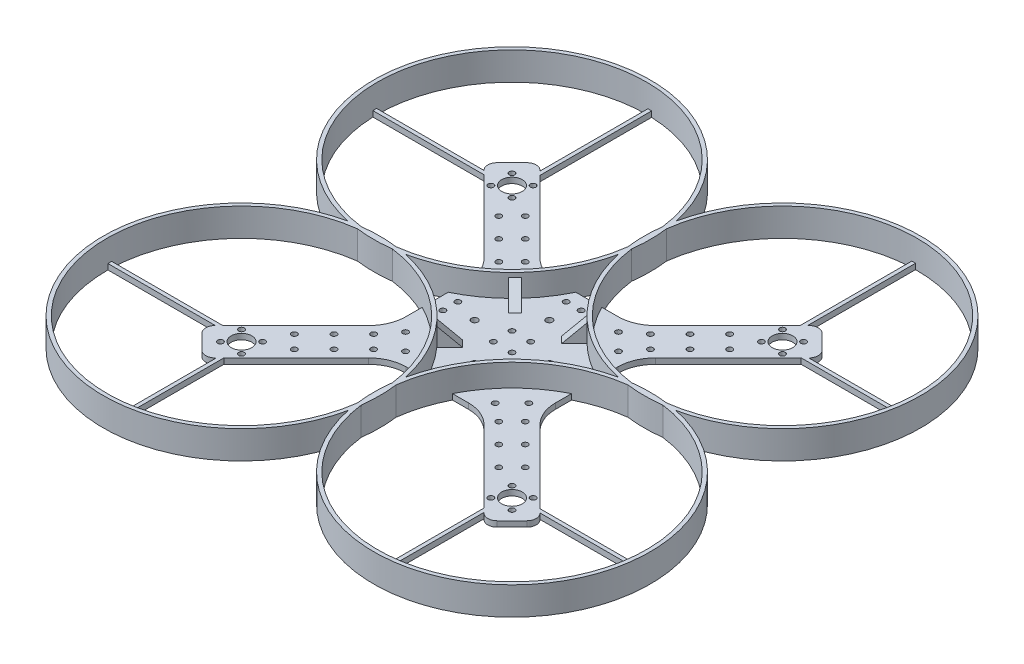
SolidWorks part; units mm, degrees
ref_plane "Front Plane" through (0, 0, 0) normal (0, 0, 1) x (1, 0, 0)
ref_plane "Top Plane" through (0, 0, 0) normal (0, 1, 0) x (1, 0, 0)
ref_plane "Right Plane" through (0, 0, 0) normal (1, 0, 0) x (0, 0, -1)
sketch "Sketch1" plane through (0, 0, 0) normal (0, 1, 0) x (1, 0, 0)
  line L0 (30.8579, 45.8579) -> (71.9645, 86.9645)
  line L1 (0, 0) -> (40, 0)
  line L2 (0, 0) -> (0, 40)
  line L3 (0, 40) -> (16.7157, 40)
  line L4 (40, 0) -> (40, 16.7157)
  line L5 (79.0355, 86.9645) -> (86.9645, 79.0355)
  line L6 (86.9645, 71.9645) -> (45.8579, 30.8579)
  arc A0 (45.8579, 30.8579) -> (40, 16.7157) centre (60, 16.7157) ccw
  arc A1 (30.8579, 45.8579) -> (16.7157, 40) centre (16.7157, 60) cw
  arc A2 (86.9645, 79.0355) -> (86.9645, 71.9645) centre (83.4289, 75.5) cw
  arc A3 (71.9645, 86.9645) -> (79.0355, 86.9645) centre (75.5, 83.4289) cw
  point P1 (83, 83)
  point P11 (40, 25)
  point P14 (25, 40)
  dimension "D7" = 20
  dimension "D8" = 5
  dimension "D1" = 40
  dimension "D2" = 40
  dimension "D3" = 45
  dimension "D4" = 25
  dimension "D5" = 25
  dimension "D6" = 83
extrude "Boss-Extrude1" add sketch "Sketch1" along normal blind 3
sketch "Sketch2" plane through (0, 3, 0) normal (0, 1, 0) x (1, 0, 0)
  line L0 (83, 83) -> (72.3934, 72.3934) construction
  line L1 (86.9645, 79.0355) -> (79.0355, 86.9645) construction
  line L2 (45.8579, 30.8579) -> (86.9645, 71.9645) construction
  circle A0 centre (72.3934, 72.3934) radius 5.5
  dimension "D1" = 11
  dimension "D2" = 15
extrude "Cut-Extrude1" cut sketch "Sketch2" against normal through all
sketch "Sketch3" plane through (0, 3, 0) normal (0, 1, 0) x (1, 0, 0)
  line L0 (72.3934, 72.3934) -> (66.7365, 66.7365) construction
  line L1 (45.8579, 30.8579) -> (86.9645, 71.9645) construction
  line L2 (72.3934, 72.3934) -> (78.0503, 66.7365) construction
  line L3 (72.3934, 72.3934) -> (66.7365, 78.0503) construction
  line L4 (72.3934, 72.3934) -> (78.0503, 78.0503) construction
  circle A0 centre (66.7365, 78.0503) radius 1.5
  circle A1 centre (66.7365, 66.7365) radius 1.5
  circle A2 centre (78.0503, 66.7365) radius 1.5
  circle A3 centre (78.0503, 78.0503) radius 1.5
  dimension "D4" = 3
  dimension "D5" = 3
  dimension "D6" = 3
  dimension "D8" = 3
  dimension "D1" = 8
  dimension "D2" = 8
  dimension "D3" = 8
  dimension "D7" = 8
extrude "Cut-Extrude2" cut sketch "Sketch3" against normal through all
sketch "Sketch4" plane through (0, 0, 0) normal (0, 1, 0) x (1, 0, 0)
  circle A0 centre (72.3934, 72.3934) radius 74
  circle A1 centre (72.3934, 72.3934) radius 72
extrude "Boss-Extrude2" add sketch "Sketch4" along normal blind 15
sketch "Sketch6" plane through (0, 3, 0) normal (0, 1, 0) x (1, 0, 0)
  line L0 (33, 4) -> (33, 24) construction
  line L1 (33, 24) -> (24, 33) construction
  line L2 (24, 33) -> (4, 33) construction
  line L3 (0, 40) -> (0, 0) construction
  line L4 (5.8602, 40) -> (0, 40) construction
  line L5 (0, 0) -> (40, 0) construction
  line L6 (40, 0) -> (40, 5.8602) construction
  line L7 (15.6066, 15.6066) -> (5, 5) construction
  line L8 (45.8579, 30.8579) -> (86.9645, 71.9645) construction
  circle A0 centre (33, 24) radius 1.5
  circle A1 centre (24, 33) radius 1.5
  circle A2 centre (4, 33) radius 1.5
  circle A3 centre (33, 4) radius 1.5
  circle A4 centre (5, 5) radius 1.5
  circle A5 centre (0, 20) radius 1.75
  circle A6 centre (20, 0) radius 1.75
  point P28 (0.2385, 3.3238)
  dimension "D1" = 4
  dimension "D7" = 5
  dimension "D11" = 3.5
  dimension "D12" = 3.5
  dimension "D2" = 7
  dimension "D3" = 20
  dimension "D4" = 4
  dimension "D5" = 20
  dimension "D6" = 7
  dimension "D8" = 5
  dimension "D9" = 15
extrude "Cut-Extrude3" cut sketch "Sketch6" against normal through all
sketch "Sketch7" plane through (0, 3, 0) normal (0, 1, 0) x (1, 0, 0)
  line L0 (54.7157, 61.7868) -> (61.7868, 54.7157) construction
  line L1 (58.2513, 58.2513) -> (83, 83) construction
  line L2 (86.9645, 79.0355) -> (79.0355, 86.9645) construction
  line L3 (45.8579, 30.8579) -> (86.9645, 71.9645) construction
  circle A0 centre (54.7157, 61.7868) radius 1.5
  circle A1 centre (61.7868, 54.7157) radius 1.5
  dimension "D1" = 10
  dimension "D2" = 35
extrude "Cut-Extrude4" cut sketch "Sketch7" against normal through all
pattern_linear "LPattern1" count 3 spacing 15 along (-0.7071, 0, 0.7071) of "Cut-Extrude4"
sketch "Sketch8" plane through (0, 3, 0) normal (0, 1, 0) x (1, 0, 0)
  line L0 (18.2404, 23.4201) -> (21.7206, 19.9399)
  line L1 (18.2404, 23.4201) -> (10.6867, 15.8663)
  line L2 (21.7206, 19.9399) -> (14.1669, 12.3861)
  line L3 (10.6867, 15.8663) -> (14.1669, 12.3861)
  line L4 (45.8579, 30.8579) -> (86.9645, 71.9645) construction
extrude "Boss-Extrude3" add sketch "Sketch8" along normal blind 10
sketch "Sketch9" plane through (0, 0, 0) normal (0, 1, 0) x (1, 0, 0)
  line L0 (70.6198, 146.3721) -> (70.6198, 145.0533) construction
  line L1 (71.6198, 82.3336) -> (69.6198, 82.3336)
  line L2 (71.6198, 82.3336) -> (71.6198, 145.0533)
  line L3 (71.6198, 145.0533) -> (69.6198, 145.0533)
  line L4 (69.6198, 82.3336) -> (69.6198, 145.0533)
  line L5 (146.3784, 70.9016) -> (145.0445, 70.9016) construction
  line L6 (82.4423, 71.9016) -> (145.0445, 71.9016)
  line L7 (82.4423, 71.9016) -> (82.4423, 69.9016)
  line L8 (82.4423, 69.9016) -> (145.0445, 69.9016)
  line L9 (145.0445, 71.9016) -> (145.0445, 69.9016)
  circle A0 centre (72.3934, 72.3934) radius 74 construction
  dimension "D1" = 2
  dimension "D2" = 2
extrude "Boss-Extrude4" add sketch "Sketch9" along normal blind 3
mirror "Mirror2" about plane through (0, 0, 0) normal (1, 0, 0) of "Boss-Extrude4", "LPattern1", "Cut-Extrude4", "Boss-Extrude2", "Boss-Extrude1", "Cut-Extrude1", "Cut-Extrude2", "Cut-Extrude3", "Boss-Extrude3" second plane through (0, 0, 0) second plane normal (0, 0, 1)
chamfer "Chamfer1" distance 10 angle 45 24 edges at (19.2242, 13, -20.9246) (14.1669, 8, -12.3861) (10.6867, 8, -15.8663) (14.1143, 13, -19.2939) (12.4268, 13, -14.1262) (17.5662, 13, -15.7854) (19.2242, 13, 20.9246) (14.1143, 13, 19.2939) (10.6867, 8, 15.8663) (17.5662, 13, 15.7854) (12.4268, 13, 14.1262) (14.1669, 8, 12.3861) (-19.2242, 13, -20.9246) (-14.1143, 13, -19.2939) (-10.6867, 8, -15.8663) (-17.5662, 13, -15.7854) (-12.4268, 13, -14.1262) (-14.1669, 8, -12.3861) (-19.2242, 13, 20.9246) (-14.1669, 8, 12.3861) (-10.6867, 8, 15.8663) (-14.1143, 13, 19.2939) (-12.4268, 13, 14.1262) (-17.5662, 13, 15.7854)
